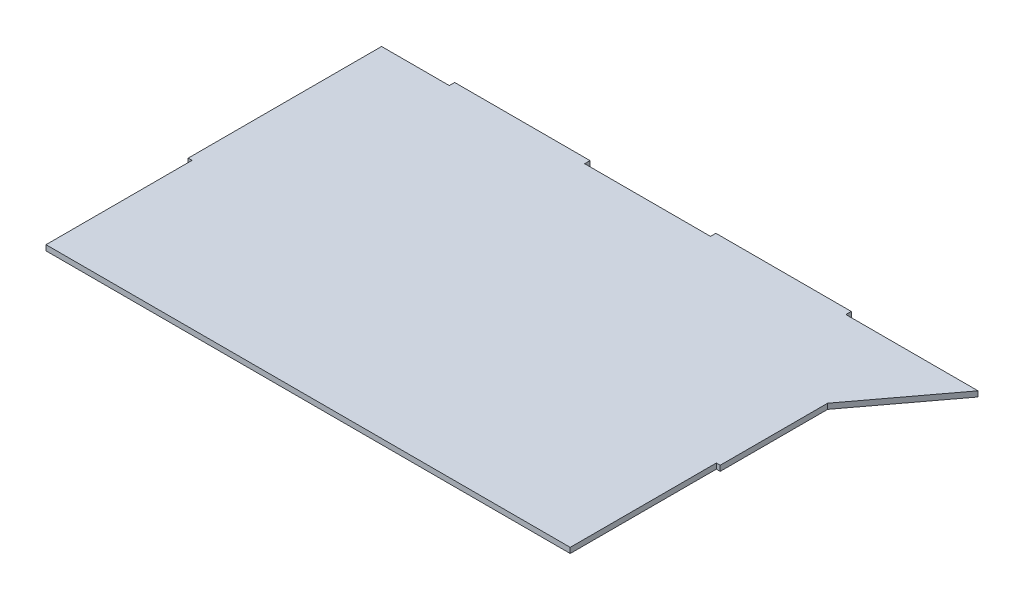
SolidWorks part; units mm, degrees
material "6061-T6 (SS)"
ref_plane "X-Y Datum" through (0, 0, 0) normal (0, 0, 1) x (1, 0, 0)
ref_plane "X-Z Datum" through (0, 0, 0) normal (0, 1, 0) x (1, 0, 0)
ref_plane "Y-Z Datum" through (0, 0, 0) normal (1, 0, 0) x (0, 0, -1)
sketch "Sketch1" plane through (0, 0, 0) normal (0, 0, 1) x (1, 0, 0)
  line L1 (-157.2306, -1.5875) -> (157.2306, -1.5875)
  line L2 (-157.2306, -1.5875) -> (-157.2306, 1.5875)
  line L3 (-157.2306, 1.5875) -> (157.2306, 1.5875)
  line L4 (157.2306, -1.5875) -> (157.2306, 1.5875)
  line L5 (-157.2306, -1.5875) -> (157.2306, 1.5875) construction
  line L6 (-157.2306, 1.5875) -> (157.2306, -1.5875) construction
  point P0 (0, 0)
  dimension "D1" = 314.4612
  dimension "D2" = 3.175
extrude "Boss-Extrude1" add sketch "Sketch1" along normal blind 200.6618
sketch "Sketch3" plane through (0, 0, 0) normal (0, 0, -1) x (-1, 0, 0)
  line L0 (-157.2306, 0) -> (-77.2306, 0) construction
  line L1 (-157.2306, -1.5875) -> (-157.2306, 1.5875) construction
  line L2 (-157.2306, 1.5875) -> (157.2306, 1.5875) construction
  line L3 (-117.2306, -1.5875) -> (-37.2306, -1.5875)
  line L4 (-117.2306, -1.5875) -> (-117.2306, 1.5875)
  line L5 (-117.2306, 1.5875) -> (-37.2306, 1.5875)
  line L6 (-37.2306, -1.5875) -> (-37.2306, 1.5875)
  line L7 (-117.2306, -1.5875) -> (-37.2306, 1.5875) construction
  line L8 (-117.2306, 1.5875) -> (-37.2306, -1.5875) construction
  line L14 (-157.2306, 1.5875) -> (-117.2306, 1.5875)
  line L15 (-157.2306, 1.5875) -> (-157.2306, -1.5875)
  line L16 (-157.2306, -1.5875) -> (-117.2306, -1.5875)
  line L17 (-117.2306, 1.5875) -> (-117.2306, -1.5875)
  line L19 (-37.2306, 1.5875) -> (-37.2306, -1.5875)
  line M3 (-157.2306, -1.5875) -> (157.2306, -1.5875)
  line M5 (157.2306, 1.5875) -> (-157.2306, 1.5875)
  dimension "D1" = 40
  dimension "D2" = 80
sketch "Sketch5" plane through (0, 1.5875, 0) normal (0, 1, 0) x (1, 0, 0)
  line L1 (-157.2306, -200.6618) -> (-154.9446, -200.6618)
  line L3 (-157.2306, -200.6618) -> (-157.2306, -114.3018)
  line L5 (-157.2306, -114.3018) -> (-154.9446, -114.3018)
  line L6 (-154.9446, -200.6618) -> (-154.9446, -114.3018)
  line M11 (-157.2306, 0) -> (-157.2306, -200.6618)
  line M12 (-157.2306, -200.6618) -> (157.2306, -200.6618)
  dimension "D1" = 86.36
  dimension "D2" = 2.286
extrude "Cut-Extrude2" cut sketch "Sketch5" against normal blind 3.175 and the other way through all contours M12 M11 region at (-156.0876, 1.5875, 157.4818)
mirror "Mirror1" about plane through (0, 0, 0) normal (1, 0, 0) of "Cut-Extrude2"
sketch "Sketch6" plane through (0, 1.5875, 0) normal (0, 1, 0) x (1, 0, 0)
  line L6 (-157.2306, -180.3418) -> (-81.0306, -180.3418)
  line L7 (-157.2306, -180.3418) -> (-157.2306, -200.6618)
  line L8 (-157.2306, -200.6618) -> (-81.0306, -200.6618)
  line L9 (-81.0306, -180.3418) -> (-81.0306, -200.6618)
  line L10 (154.9446, -200.6618) -> (-154.9446, -200.6618) construction
  line L11 (-157.2306, -114.3018) -> (-157.2306, 0) construction
  line L13 (154.9446, -200.6618) -> (-81.0306, -200.6618)
  line L14 (154.9446, -200.6618) -> (154.9446, -180.3418)
  line L15 (154.9446, -180.3418) -> (-81.0306, -180.3418)
  line L16 (-81.0306, -200.6618) -> (-81.0306, -180.3418)
  line M18 (-154.9446, -114.3018) -> (-154.9446, -200.6618)
  line M19 (-154.9446, -200.6618) -> (154.9446, -200.6618)
  dimension "D1" = 76.2
  dimension "D2" = 20.32
extrude "Cut-Extrude4" [suppressed] cut sketch "Sketch6" against normal through all contours L9 L6 M18 M19
sketch "Sketch7" [suppressed] plane through (0, 1.5875, 0) normal (0, 1, 0) x (1, 0, 0)
  line L1 (-81.2823, -215.455) -> (155.1963, -215.455)
  line L2 (-81.2823, -215.455) -> (-81.2823, -235.775)
  line L3 (-81.2823, -235.775) -> (155.1963, -235.775)
  line L4 (155.1963, -215.455) -> (155.1963, -235.775)
extrude "Cut-Extrude5" [suppressed] cut sketch "Sketch7" against normal through all
sketch "Sketch8" [suppressed] plane through (0, 1.5875, 0) normal (0, 1, 0) x (1, 0, 0)
  line L0 (155.1963, -235.775) -> (-155.1963, -235.775) construction
  line L1 (157.4823, -215.455) -> (81.2823, -215.455)
  line L2 (157.4823, -215.455) -> (157.4823, -235.775)
  line L3 (157.4823, -235.775) -> (81.2823, -235.775)
  line L4 (81.2823, -215.455) -> (81.2823, -235.775)
  line L5 (157.4823, -117.411) -> (157.4823, -3.175) construction
  dimension "D1" = 20.32
  dimension "D2" = 76.2
extrude "Cut-Extrude6" [suppressed] cut sketch "Sketch8" against normal through all
sketch "Sketch9" [suppressed] plane through (0, 0, 215.455) normal (0, 0, 1) x (1, 0, 0)
  line L4 (155.1963, 1.5875) -> (-155.1963, 1.5875)
  line L5 (-155.1963, 1.5875) -> (-155.1963, -1.5875)
  line L6 (-155.1963, -1.5875) -> (155.1963, -1.5875)
  line L7 (155.1963, -1.5875) -> (155.1963, 1.5875)
  line L8 (155.1963, 1.5875) -> (-155.1963, 1.5875)
  line L9 (-155.1963, 1.5875) -> (-155.1963, -1.5875)
  line L10 (-155.1963, -1.5875) -> (155.1963, -1.5875)
  line L11 (155.1963, -1.5875) -> (155.1963, 1.5875)
  dimension "D1" = 0
extrude "Cut-Extrude7" [suppressed] cut sketch "Sketch9" against normal blind 11.68
extrude "Boss-Extrude2" add sketch "Sketch3" along normal blind 3.175 contours L6 L4 M3 M5 region at (77.2306, 0, 0)
pattern_linear "LPattern2" count 2 spacing 154.43 along (-1, 0, 0) of "Boss-Extrude2"
sketch "Sketch10" plane through (0, -1.5875, 0) normal (0, -1, 0) x (1, 0, 0)
  line L8 (157.2306, 0) -> (195.3306, 0)
  line L9 (195.3306, 0) -> (157.2306, 50.8)
  line L10 (157.2306, 114.3018) -> (157.2306, 0) construction
  line L11 (157.2306, 50.8) -> (157.2306, 0)
  dimension "D1" = 50.8
  dimension "D2" = 38.1
extrude "Boss-Extrude3" add sketch "Sketch10" against normal blind 3.175
sketch "Sketch11" [suppressed] plane through (0, 0, 0) normal (0, 0, -1) x (-1, 0, 0)
  line L1 (37.2652, -1.5875) -> (117.2652, -1.5875)
  line L2 (37.2652, -1.5875) -> (37.2652, 1.5875)
  line L3 (37.2652, 1.5875) -> (117.2652, 1.5875)
  line L4 (117.2652, -1.5875) -> (117.2652, 1.5875)
  line L5 (-117.1668, -1.5875) -> (-37.1668, -1.5875)
  line L6 (-117.1668, -1.5875) -> (-117.1668, 1.5875)
  line L7 (-117.1668, 1.5875) -> (-37.1668, 1.5875)
  line L8 (-37.1668, -1.5875) -> (-37.1668, 1.5875)
extrude "Boss-Extrude4" [suppressed] add sketch "Sketch11" along normal blind 3.175
